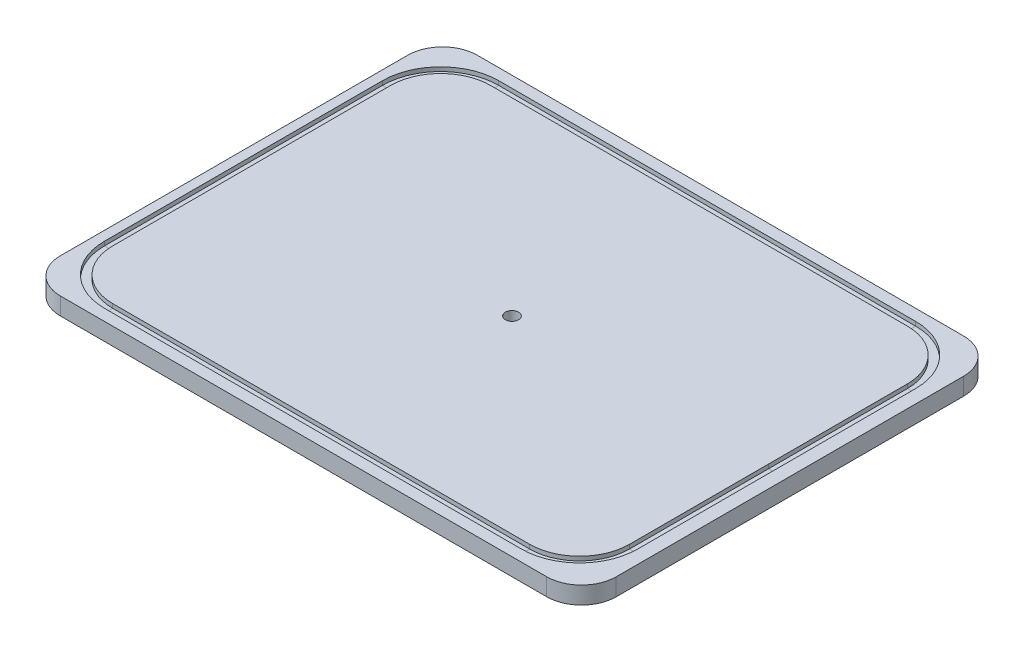
SolidWorks part; units mm, degrees
ref_plane "Front Plane" through (0, 0, 0) normal (0, 0, 1) x (1, 0, 0)
ref_plane "Top Plane" through (0, 0, 0) normal (0, 1, 0) x (1, 0, 0)
ref_plane "Right Plane" through (0, 0, 0) normal (1, 0, 0) x (0, 0, -1)
sketch "Sketch1" plane through (0, 0, 0) normal (0, 1, 0) x (1, 0, 0)
  line L0 (0, -11.3506) -> (0, 11.3506) construction
  line L1 (-11.3506, 0) -> (11.3506, 0) construction
  line L12 (-101.6, 63.5) -> (-101.6, -63.5)
  line L13 (-88.9, -76.2) -> (88.9, -76.2)
  line L14 (101.6, -63.5) -> (101.6, 63.5)
  line L15 (88.9, 76.2) -> (-88.9, 76.2)
  arc A0 (88.9, -76.2) -> (101.6, -63.5) centre (88.9, -63.5) ccw
  arc A1 (101.6, 63.5) -> (88.9, 76.2) centre (88.9, 63.5) ccw
  arc A2 (-101.6, -63.5) -> (-88.9, -76.2) centre (-88.9, -63.5) ccw
  arc A3 (-101.6, 63.5) -> (-88.9, 76.2) centre (-88.9, 63.5) cw
  point P8 (101.6, 76.2)
  point P11 (-101.6, -76.2)
  point P14 (-101.6, 76.2)
  point P15 (0, 76.2)
  point P18 (101.6, 0)
  dimension "D3" = 12.7
  dimension "D1" = 203.2
  dimension "D2" = 152.4
extrude "main body" add sketch "Sketch1" along normal blind 6.35
hole_wizard "#10-32 Tapped Hole2" positions "Sketch26" profile "Sketch27" tap size "#10-32" standard "ANSI Inch" end condition through all
sketch "Sketch26" plane through (0, 0, 0) normal (0, -1, 0) x (1, 0, 0)
  line L0 (-88.9, 76.2) -> (88.9, 76.2) construction
  line L1 (-101.6, -63.5) -> (-101.6, 63.5) construction
  point P0 (0, 0)
  point P4 (0, 76.2)
  point P7 (-101.6, 0)
sketch "Sketch27" plane through (0, 0, 0) normal (1, 0, 0) x (0, 0, -1)
  line L0 (0, 0) -> (0, 6.35)
  line L1 (0, 6.35) -> (2.413, 6.35)
  line L2 (2.413, 6.35) -> (2.413, 0)
  line L5 (2.413, 0) -> (0, 0)
  line L11 (0, -6.35) -> (0, 107.95) construction
  dimension "Thread Major Dia." = 4.826
  dimension "Thru Tap Drill Depth" = 6.35
sketch "GasketPath" plane through (0, 6.35, 0) normal (0, 1, 0) x (1, 0, 0)
  line L42 (-101.6, 63.5) -> (-101.6, -63.5) construction
  line L50 (-95.6, 50.8) -> (-95.6, -50.8)
  line L51 (-76.9, -69.5) -> (75.5, -69.5)
  line L52 (94.2, -50.8) -> (94.2, 50.8)
  line L53 (75.5, 69.5) -> (-76.9, 69.5)
  arc A49 (-95.6, -50.8) -> (-76.9, -69.5) centre (-76.9, -50.8) ccw
  arc A50 (75.5, -69.5) -> (94.2, -50.8) centre (75.5, -50.8) ccw
  arc A51 (94.2, 50.8) -> (75.5, 69.5) centre (75.5, 50.8) ccw
  arc A52 (-76.9, 69.5) -> (-95.6, 50.8) centre (-76.9, 50.8) ccw
  point P2 (-95.6, 0)
  dimension "D1" = 6
sketch "GasketProfile" plane through (0, 0, 0) normal (0, 0, -1) x (-1, 0, 0)
  line L1 (-93.75, 4.85) -> (-96.75, 4.85)
  line L2 (-93.75, 4.85) -> (-93.75, 7.85)
  line L3 (-93.75, 7.85) -> (-96.75, 7.85)
  line L4 (-96.75, 4.85) -> (-96.75, 7.85)
  line L5 (-93.75, 4.85) -> (-96.75, 7.85) construction
  line L6 (-93.75, 7.85) -> (-96.75, 4.85) construction
  line L8 (2.413, 6.35) -> (-2.413, 6.35) construction
  point P0 (-95.25, 6.35)
  dimension "D1" = 3
sweep "GasketInsert" cut profiles "GasketProfile" path "GasketPath"
equation "\"BodyLength\"=8"
equation "\"BodyWidth\"=6"
equation "\"D2@Sketch1\"=\"BodyWidth\""
equation "\"D1@Sketch1\"= \"BodyLength\""
equation "\"SealingEdge\"=0.5"
equation "\"ShellHeight\"=0.25"
equation "\"D1@main body\"=\"ShellHeight\""
